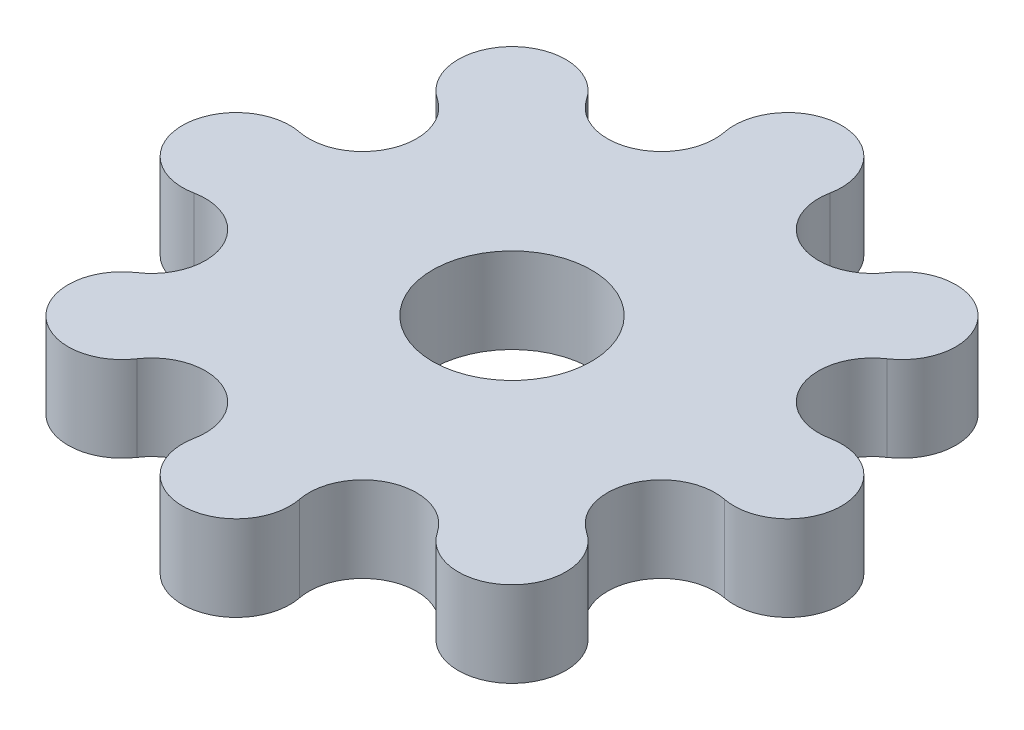
SolidWorks part; units mm, degrees
material "6061-T6 (SS)"
ref_plane "Front Plane" through (0, 0, 0) normal (0, 0, 1) x (1, 0, 0)
ref_plane "Top Plane" through (0, 0, 0) normal (0, 1, 0) x (1, 0, 0)
ref_plane "Right Plane" through (0, 0, 0) normal (1, 0, 0) x (0, 0, -1)
sketch "Sketch1" plane through (0, 0, 0) normal (0, 1, 0) x (1, 0, 0)
  line L0 (0, 0) -> (0, 10.2517) construction
  circle A1 centre (0, 0) radius 4
  arc A2 (1.9616, 9.8615) -> (-1.9616, 9.8615) centre (0, 10.2517) ccw
  arc A3 (1.9616, 9.8615) -> (5.5861, 8.3602) centre (3.9231, 9.4713) ccw
  arc A4 (8.3602, 5.5861) -> (5.5861, 8.3602) centre (7.249, 7.249) ccw
  arc A5 (8.3602, 5.5861) -> (9.8615, 1.9616) centre (9.4713, 3.9231) ccw
  arc A6 (9.8615, -1.9616) -> (9.8615, 1.9616) centre (10.2517, 0) ccw
  arc A7 (9.8615, -1.9616) -> (8.3602, -5.5861) centre (9.4713, -3.9231) ccw
  arc A8 (5.5861, -8.3602) -> (8.3602, -5.5861) centre (7.249, -7.249) ccw
  arc A9 (5.5861, -8.3602) -> (1.9616, -9.8615) centre (3.9231, -9.4713) ccw
  arc A10 (-1.9616, -9.8615) -> (1.9616, -9.8615) centre (0, -10.2517) ccw
  arc A11 (-1.9616, -9.8615) -> (-5.5861, -8.3602) centre (-3.9231, -9.4713) ccw
  arc A12 (-8.3602, -5.5861) -> (-5.5861, -8.3602) centre (-7.249, -7.249) ccw
  arc A13 (-8.3602, -5.5861) -> (-9.8615, -1.9616) centre (-9.4713, -3.9231) ccw
  arc A14 (-9.8615, 1.9616) -> (-9.8615, -1.9616) centre (-10.2517, 0) ccw
  arc A15 (-9.8615, 1.9616) -> (-8.3602, 5.5861) centre (-9.4713, 3.9231) ccw
  arc A16 (-5.5861, 8.3602) -> (-8.3602, 5.5861) centre (-7.249, 7.249) ccw
  arc A17 (-5.5861, 8.3602) -> (-1.9616, 9.8615) centre (-3.9231, 9.4713) ccw
  point P39 (0, 0)
  point P41 (0, 0)
  dimension "D1" = 8
  dimension "D2" = 4
  dimension "D4" = 16
extrude "Boss-Extrude1" add sketch "Sketch1" along normal blind 3.175
sketch "Sketch2" plane through (0, 3.175, 0) normal (0, 1, 0) x (1, 0, 0)
  circle A0 centre (0, 0) radius 4 construction
  circle A1 centre (0, 0) radius 4
  circle A2 centre (0, 0) radius 2.95
  dimension "D1" = 5.9
extrude "Boss-Extrude2" add sketch "Sketch2" against normal up to surface (3.175 mm away) up to face at (0, 0, 0)
